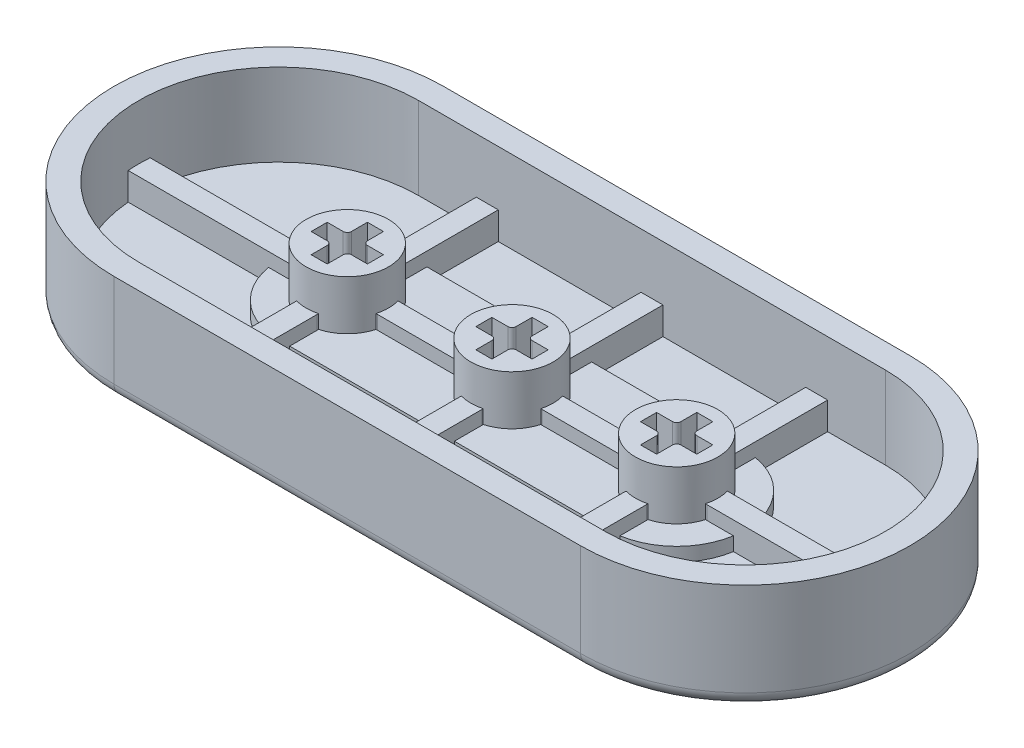
SolidWorks part; units mm, degrees
ref_plane "Front Plane" through (0, 0, 0) normal (0, 0, 1) x (1, 0, 0)
ref_plane "Top Plane" through (0, 0, 0) normal (0, 1, 0) x (1, 0, 0)
ref_plane "Right Plane" through (0, 0, 0) normal (1, 0, 0) x (0, 0, -1)
sketch "Sketch1" plane through (0, 0, 0) normal (0, 1, 0) x (1, 0, 0)
  line L0 (17, 0) -> (-17, 0) construction
  line L1 (17, -12) -> (-17, -12)
  line L2 (17, 12) -> (-17, 12)
  arc A1 (17, -12) -> (17, 12) centre (17, 0) ccw
  arc A2 (-17, 12) -> (-17, -12) centre (-17, 0) ccw
  point P5 (0, 0)
  point P10 (-29, 0)
  point P11 (29, 0)
  dimension "D2" = 12
  dimension "D3" = 58
extrude "button top" add sketch "Sketch1" along normal blind 1.8
sketch "Sketch2" plane through (0, 1.8, 0) normal (0, 1, 0) x (1, 0, 0)
  line L0 (-17, 0) -> (17, 0) construction
  line L1 (-17, 12) -> (17, 12)
  line L2 (-17, -12) -> (17, -12)
  line L3 (-17, 0) -> (17, 0) construction
  line L4 (-17, 10.2) -> (17, 10.2)
  line L5 (-17, -10.2) -> (17, -10.2)
  arc A2 (-17, 12) -> (-17, -12) centre (-17, 0) ccw
  arc A6 (17, -12) -> (17, 12) centre (17, 0) ccw
  arc A7 (17, -12) -> (17, 12) centre (17, 0) ccw construction
  arc A8 (-17, 10.2) -> (-17, -10.2) centre (-17, 0) ccw
  arc A9 (17, -10.2) -> (17, 10.2) centre (17, 0) ccw
  point P2 (0, 0)
  point P15 (0, 0)
  dimension "D1" = 1.8
extrude "button walls" add sketch "Sketch2" along normal blind 6
sketch "Sketch5" plane through (0, 1.8, 0) normal (0, 1, 0) x (1, 0, 0)
  line L0 (-12, 0) -> (12, 0) construction
  line L1 (-12, 5) -> (12, 5)
  line L2 (-12, -5) -> (12, -5)
  arc A0 (-12, 5) -> (-12, -5) centre (-12, 0) ccw
  arc A1 (12, -5) -> (12, 5) centre (12, 0) ccw
  point P3 (0, 0)
  point P8 (0, 0)
  dimension "D1" = 5
  dimension "D2" = 24
extrude "offset" add sketch "Sketch5" along normal blind 1
sketch "Sketch3" plane through (0, 1.8, 0) normal (0, 1, 0) x (1, 0, 0)
  line L0 (0, -2.05) -> (0, 2.05) construction
  line L1 (-2.05, 0) -> (2.05, 0) construction
  line L2 (-0.585, 0.885) -> (-0.585, 2.05)
  line L3 (-0.585, -2.05) -> (0.585, -2.05)
  line L4 (-0.585, -2.05) -> (-0.585, -0.885)
  line L5 (-0.585, 2.05) -> (0.585, 2.05)
  line L6 (0.585, -2.05) -> (0.585, -0.885)
  line L7 (-0.585, -2.05) -> (0.585, 2.05) construction
  line L8 (-0.585, 2.05) -> (0.585, -2.05) construction
  line L9 (-2.05, -0.585) -> (-0.885, -0.585)
  line L10 (-2.05, -0.585) -> (-2.05, 0.585)
  line L11 (-2.05, 0.585) -> (-0.885, 0.585)
  line L12 (2.05, -0.585) -> (2.05, 0.585)
  line L13 (-2.05, -0.585) -> (2.05, 0.585) construction
  line L14 (-2.05, 0.585) -> (2.05, -0.585) construction
  line L15 (0.885, 0.585) -> (2.05, 0.585)
  line L16 (0.585, 0.885) -> (0.585, 2.05)
  line L17 (0.885, -0.585) -> (2.05, -0.585)
  line L18 (11.415, 0.885) -> (11.415, 2.05)
  line L19 (11.415, -2.05) -> (12.585, -2.05)
  line L20 (11.415, -2.05) -> (11.415, -0.885)
  line L21 (11.415, 2.05) -> (12.585, 2.05)
  line L22 (12.585, -2.05) -> (12.585, -0.885)
  line L23 (9.95, -0.585) -> (11.115, -0.585)
  line L24 (9.95, -0.585) -> (9.95, 0.585)
  line L25 (9.95, 0.585) -> (11.115, 0.585)
  line L26 (14.05, -0.585) -> (14.05, 0.585)
  line L27 (12.885, 0.585) -> (14.05, 0.585)
  line L28 (12.585, 0.885) -> (12.585, 2.05)
  line L29 (12.885, -0.585) -> (14.05, -0.585)
  line L30 (12, -2.05) -> (12, 2.05) construction
  line L31 (9.95, 0) -> (14.05, 0) construction
  line L32 (11.415, -2.05) -> (12.585, 2.05) construction
  line L33 (11.415, 2.05) -> (12.585, -2.05) construction
  line L34 (9.95, -0.585) -> (14.05, 0.585) construction
  line L35 (9.95, 0.585) -> (14.05, -0.585) construction
  line L36 (-12.585, 0.885) -> (-12.585, 2.05)
  line L37 (-12.585, -2.05) -> (-11.415, -2.05)
  line L38 (-12.585, -2.05) -> (-12.585, -0.885)
  line L39 (-12.585, 2.05) -> (-11.415, 2.05)
  line L40 (-11.415, -2.05) -> (-11.415, -0.885)
  line L41 (-14.05, -0.585) -> (-12.885, -0.585)
  line L42 (-14.05, -0.585) -> (-14.05, 0.585)
  line L43 (-14.05, 0.585) -> (-12.885, 0.585)
  line L44 (-9.95, -0.585) -> (-9.95, 0.585)
  line L45 (-11.115, 0.585) -> (-9.95, 0.585)
  line L46 (-11.415, 0.885) -> (-11.415, 2.05)
  line L47 (-11.115, -0.585) -> (-9.95, -0.585)
  line L48 (-12, -2.05) -> (-12, 2.05) construction
  line L49 (-14.05, 0) -> (-9.95, 0) construction
  line L50 (-12.585, -2.05) -> (-11.415, 2.05) construction
  line L51 (-12.585, 2.05) -> (-11.415, -2.05) construction
  line L52 (-14.05, -0.585) -> (-9.95, 0.585) construction
  line L53 (-14.05, 0.585) -> (-9.95, -0.585) construction
  circle A0 centre (0, 0) radius 3
  arc A1 (-0.585, -0.885) -> (-0.885, -0.585) centre (-0.885, -0.885) ccw
  arc A2 (0.585, -0.885) -> (0.885, -0.585) centre (0.885, -0.885) cw
  arc A3 (0.885, 0.585) -> (0.585, 0.885) centre (0.885, 0.885) cw
  arc A4 (-0.585, 0.885) -> (-0.885, 0.585) centre (-0.885, 0.885) cw
  circle A5 centre (12, 0) radius 3
  arc A6 (11.415, -0.885) -> (11.115, -0.585) centre (11.115, -0.885) ccw
  arc A7 (12.585, -0.885) -> (12.885, -0.585) centre (12.885, -0.885) cw
  arc A8 (12.885, 0.585) -> (12.585, 0.885) centre (12.885, 0.885) cw
  arc A9 (11.415, 0.885) -> (11.115, 0.585) centre (11.115, 0.885) cw
  circle A10 centre (-12, 0) radius 3
  arc A11 (-12.585, -0.885) -> (-12.885, -0.585) centre (-12.885, -0.885) ccw
  arc A12 (-11.415, -0.885) -> (-11.115, -0.585) centre (-11.115, -0.885) cw
  arc A13 (-11.115, 0.585) -> (-11.415, 0.885) centre (-11.115, 0.885) cw
  arc A14 (-12.585, 0.885) -> (-12.885, 0.585) centre (-12.885, 0.885) cw
  point P6 (0, 0)
  point P9 (0, 0)
  point P22 (2.05, 0)
  point P24 (0, 2.05)
  point P29 (0.585, -0.585)
  point P32 (0.585, 0.585)
  point P40 (12, 0)
  point P43 (12, 0)
  point P69 (-12, 0)
  point P72 (-12, 0)
  dimension "D1" = 6
  dimension "D4" = 0.3
  dimension "D2" = 4.1
  dimension "D3" = 1.17
  dimension "D5" = 2
  dimension "D6" = 2
extrude "stem housing" add sketch "Sketch3" along normal blind 3.6 from surface starting at face at (0, 2.8, 0)
sketch "Sketch4" plane through (0, 1.8, 0) normal (0, 1, 0) x (1, 0, 0)
  line L0 (0, 3) -> (0, 10.2) construction
  line L1 (-0.8, 3) -> (-0.8, 10.2)
  line L2 (0.8, 3) -> (0.8, 10.2)
  line L3 (0, -4.29) -> (0, 4.29) construction
  line L6 (-15, 0) -> (-27.2, 0) construction
  line L9 (9, 0) -> (3, 0) construction
  line L12 (9, 0.8) -> (3, 0.8)
  line L15 (9, -0.8) -> (3, -0.8)
  line L18 (15, 0) -> (27.2, 0) construction
  line L19 (15, -0.8) -> (27.2, -0.8)
  line L20 (15, 0.8) -> (27.2, 0.8)
  line L21 (12, 3) -> (12, 10.2) construction
  line L22 (11.2, 3) -> (11.2, 10.2)
  line L23 (12.8, 3) -> (12.8, 10.2)
  line L24 (-12, 3) -> (-12, 10.2) construction
  line L25 (-12.8, 3) -> (-12.8, 10.2)
  line L26 (-11.2, 3) -> (-11.2, 10.2)
  line L27 (-15, -0.8) -> (-27.2, -0.8)
  line L28 (-15, 0.8) -> (-27.2, 0.8)
  line L29 (-4.29, 0) -> (4.29, 0) construction
  line L32 (-9, 0) -> (-3, 0) construction
  line L33 (-9, 0.8) -> (-3, 0.8)
  line L34 (-9, -0.8) -> (-3, -0.8)
  line L35 (0, -3) -> (0, -10.2) construction
  line L36 (-0.8, -3) -> (-0.8, -10.2)
  line L37 (0.8, -3) -> (0.8, -10.2)
  line L38 (12, -3) -> (12, -10.2) construction
  line L39 (11.2, -3) -> (11.2, -10.2)
  line L40 (12.8, -3) -> (12.8, -10.2)
  line L41 (-12, -3) -> (-12, -10.2) construction
  line L42 (-12.8, -3) -> (-12.8, -10.2)
  line L43 (-11.2, -3) -> (-11.2, -10.2)
  line L44 (17, 10.2) -> (-17, 10.2) construction
  circle A0 centre (0, 0) radius 3 construction
  circle A1 centre (0, 0) radius 3 construction
  arc A3 (-0.8, 3) -> (0.8, 3) centre (0, 3) ccw
  arc A4 (0.8, 10.2) -> (-0.8, 10.2) centre (0, 10.2) ccw
  arc A15 (9, 0.8) -> (9, -0.8) centre (9, 0) cw
  arc A16 (3, -0.8) -> (3, 0.8) centre (3, 0) cw
  arc A17 (15, -0.8) -> (15, 0.8) centre (15, 0) cw
  arc A18 (27.2, 0.8) -> (27.2, -0.8) centre (27.2, 0) cw
  arc A19 (11.2, 3) -> (12.8, 3) centre (12, 3) ccw
  arc A20 (12.8, 10.2) -> (11.2, 10.2) centre (12, 10.2) ccw
  arc A21 (-12.8, 3) -> (-11.2, 3) centre (-12, 3) ccw
  arc A22 (-11.2, 10.2) -> (-12.8, 10.2) centre (-12, 10.2) ccw
  circle A23 centre (-12, 0) radius 3 construction
  circle A24 centre (-12, 0) radius 3 construction
  arc A25 (-17, 10.2) -> (-17, -10.2) centre (-17, 0) ccw construction
  arc A26 (-15, -0.8) -> (-15, 0.8) centre (-15, 0) ccw
  arc A27 (-27.2, 0.8) -> (-27.2, -0.8) centre (-27.2, 0) ccw
  arc A33 (-9, 0.8) -> (-9, -0.8) centre (-9, 0) ccw
  arc A34 (-3, -0.8) -> (-3, 0.8) centre (-3, 0) ccw
  arc A35 (-0.8, -3) -> (0.8, -3) centre (0, -3) cw
  arc A36 (0.8, -10.2) -> (-0.8, -10.2) centre (0, -10.2) cw
  arc A37 (11.2, -3) -> (12.8, -3) centre (12, -3) cw
  arc A38 (12.8, -10.2) -> (11.2, -10.2) centre (12, -10.2) cw
  arc A39 (-12.8, -3) -> (-11.2, -3) centre (-12, -3) cw
  arc A40 (-11.2, -10.2) -> (-12.8, -10.2) centre (-12, -10.2) cw
  point P9 (0, 6.6)
  point P19 (6, 0)
  point P33 (21.1, 0)
  point P40 (12, 6.6)
  point P47 (-12, 6.6)
  point P55 (0, -6.6)
  point P59 (-21.1, 0)
  point P69 (12, -6.6)
  point P76 (-12, -6.6)
  point P81 (-6, 0)
  dimension "D1" = 1.6
  dimension "D3" = 2
  dimension "D4" = 12
  dimension "D5" = 12
  dimension "D2" = 2
extrude "Boss-Extrude4" add sketch "Sketch4" along normal blind 2
fillet "Fillet1" radius 1 4 edges at (0, 0, -12) (-29, 0, 0) (0, 0, 12) (29, 0, 0)
